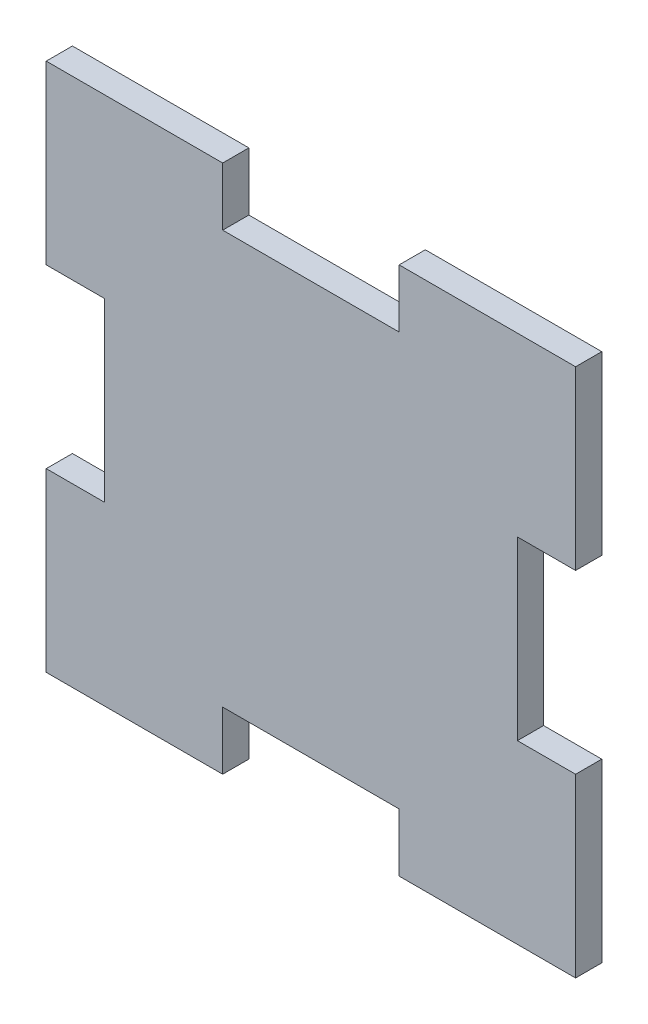
SolidWorks part; units mm, degrees
ref_plane "Front Plane" through (0, 0, 0) normal (0, 0, 1) x (1, 0, 0)
ref_plane "Top Plane" through (0, 0, 0) normal (0, 1, 0) x (1, 0, 0)
ref_plane "Right Plane" through (0, 0, 0) normal (1, 0, 0) x (0, 0, -1)
sketch "Sketch1" plane through (0, 0, 0) normal (0, 0, 1) x (1, 0, 0)
  line L2 (1.1204, 63.3976) -> (1.1204, 32.2376)
  line L5 (31.0404, 2.3176) -> (62.2004, 2.3176)
  line L6 (92.1204, 32.2376) -> (92.1204, 62.1576)
  line L8 (1.1204, 93.3176) -> (1.1204, 63.3976)
  line L9 (60.9604, 93.3176) -> (31.0404, 93.3176)
  line L12 (1.1204, 2.3176) -> (1.1204, 32.2376)
  line L15 (1.1204, 93.3176) -> (31.0404, 93.3176)
  line L19 (92.1204, 93.3176) -> (60.9604, 93.3176)
  line L22 (92.1204, 93.3176) -> (92.1204, 62.1576)
  line L27 (92.1204, 2.3176) -> (62.2004, 2.3176)
  line L28 (92.1204, 32.2376) -> (92.1204, 2.3176)
  line L33 (1.1204, 2.3176) -> (31.0404, 2.3176)
  dimension "D1" = 91
  dimension "D2" = 91
extrude "Boss-Extrude1" add sketch "Sketch1" along normal blind 4.5
sketch "Sketch2" plane through (0, 0, 4.5) normal (0, 0, 1) x (1, 0, 0)
  line L0 (1.1204, 47.8176) -> (50001.1204, 47.8176) construction
  line L1 (1.1204, 32.651) -> (1.1204, 62.9843)
  line L2 (46.6204, 93.3176) -> (46.6204, 2.3176) construction
  line L3 (92.1204, 32.651) -> (82.1204, 32.651)
  line L4 (1.1204, 93.3176) -> (1.1204, 2.3176) construction
  line L5 (92.1204, 2.3176) -> (92.1204, 93.3176) construction
  line L6 (92.1204, 32.651) -> (92.1204, 62.9843)
  line L7 (92.1204, 93.3176) -> (1.1204, 93.3176) construction
  line L8 (92.1204, 62.9843) -> (82.1204, 62.9843)
  line L9 (82.1204, 32.651) -> (82.1204, 62.9843)
  line L10 (1.1204, 2.3176) -> (92.1204, 2.3176) construction
  line L11 (1.1204, 32.651) -> (11.1204, 32.651)
  line L12 (11.1204, 32.651) -> (11.1204, 62.9843)
  line L13 (1.1204, 62.9843) -> (11.1204, 62.9843)
  line L14 (31.4537, 93.3176) -> (1.1204, 93.3176) construction
  line L15 (31.4537, 93.3176) -> (61.787, 93.3176)
  line L16 (92.1204, 93.3176) -> (92.1204, 62.9843) construction
  line L17 (31.4537, 93.3176) -> (31.4537, 83.3176)
  line L18 (31.4537, 83.3176) -> (61.787, 83.3176)
  line L19 (61.787, 93.3176) -> (61.787, 83.3176)
  line L20 (92.1204, 93.3176) -> (61.787, 93.3176) construction
  line L21 (92.1204, 32.651) -> (92.1204, 2.3176) construction
  line L22 (31.4537, 12.3176) -> (61.787, 12.3176)
  line L23 (61.787, 2.3176) -> (61.787, 12.3176)
  line L24 (31.4537, 2.3176) -> (61.787, 2.3176)
  line L25 (31.4537, 2.3176) -> (31.4537, 12.3176)
  point P10 (1.1204, 47.8176)
  point P13 (92.1204, 47.8176)
  point P26 (46.1848, 47.8176)
  dimension "D1" = 10
  dimension "D2" = 10
extrude "Cut-Extrude1" cut sketch "Sketch2" against normal through all
equation "\"mdf\"=\"mdf@fmv1.assembly\""
equation "\"D1@Boss-Extrude1\"=\"mdf\""
equation "\"D1@Sketch1\" = 100-2*\"mdf\""
equation "\"D2@Sketch1\" = 100-2*\"mdf\""
